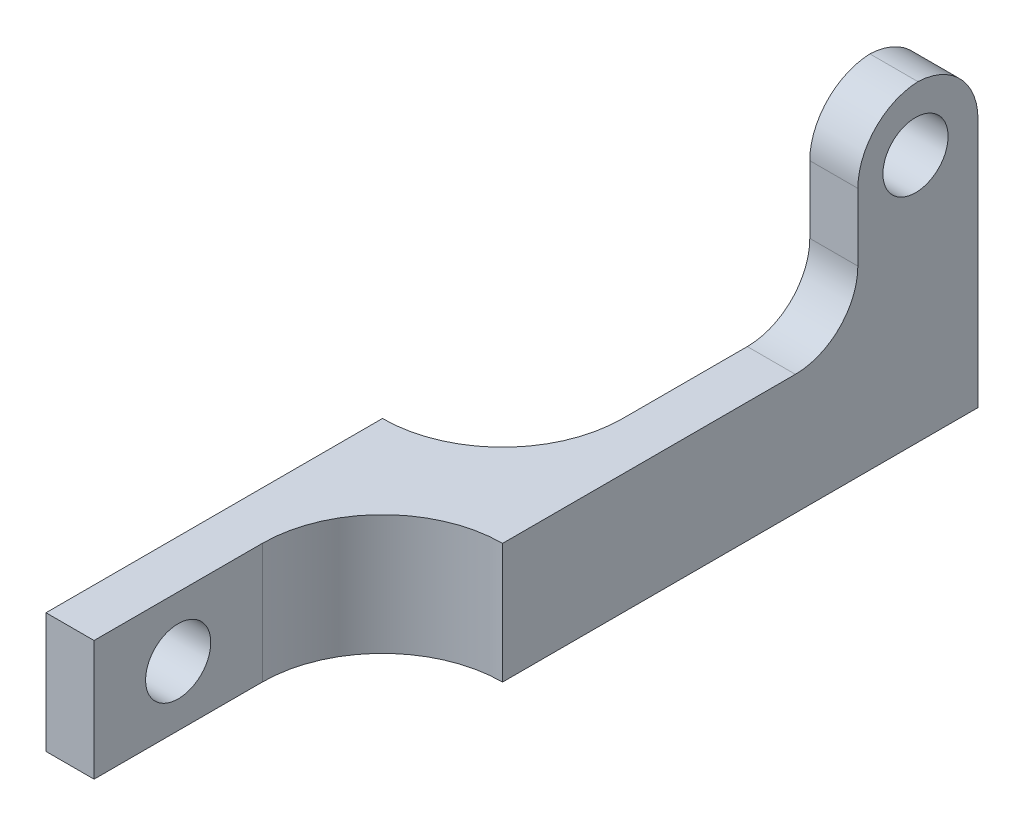
SolidWorks part; units mm, degrees
ref_plane "Front Plane" through (0, 0, 0) normal (0, 0, 1) x (1, 0, 0)
ref_plane "Top Plane" through (0, 0, 0) normal (0, 1, 0) x (1, 0, 0)
ref_plane "Right Plane" through (0, 0, 0) normal (1, 0, 0) x (0, 0, -1)
sketch "Sketch1" plane through (0, 0, 0) normal (0, 1, 0) x (1, 0, 0)
  line L0 (0, 0) -> (0, 22.225)
  line L1 (0, 22.225) -> (7.9375, 22.225)
  line L2 (7.9375, 22.225) -> (7.9375, 50.4584)
  line L3 (7.9375, 50.4584) -> (11.1125, 50.4584)
  line L4 (11.1125, 50.4584) -> (11.1125, 19.05)
  line L5 (11.1125, 19.05) -> (3.175, 19.05)
  line L6 (3.175, 19.05) -> (3.175, 0)
  line L7 (3.175, 0) -> (0, 0)
  dimension "D1" = 3.175
  dimension "D2" = 3.175
  dimension "D3" = 19.05
  dimension "D4" = 50.4584
  dimension "D5" = 7.9375
extrude "Boss-Extrude1" add sketch "Sketch1" along normal blind 7.9375
fillet "Fillet1" radius 7.9375 2 edges at (7.9375, 3.9688, -22.225) (3.175, 3.9688, -19.05)
sketch "Sketch6" plane through (0, 7.9375, 0) normal (0, 1, 0) x (1, 0, 0)
  line L0 (7.9375, 50.4584) -> (7.9375, 30.1625) construction
  line L1 (11.1125, 50.4584) -> (7.9375, 50.4584)
  line L2 (11.1125, 50.4584) -> (11.1125, 42.5209)
  line L3 (11.1125, 42.5209) -> (7.9375, 42.5209)
  line L4 (7.9375, 50.4584) -> (7.9375, 42.5209)
  dimension "D1" = 7.9375
extrude "Boss-Extrude2" add sketch "Sketch6" along normal blind 12.7
fillet "Fillet2" radius 4.1275 2 edges at (9.525, 20.6375, -50.4584) (9.525, 20.6375, -42.5209)
fillet "Fillet3" radius 4.1275 1 edges at (9.525, 7.9375, -42.5209)
hole_wizard "#6 Clearance Hole1" positions "Sketch2" profile "Sketch3" hole size "#6" standard "ANSI Inch" end condition through all
sketch "Sketch2" plane through (0, 0, 0) normal (1, 0, 0) x (0, 0, -1)
  line L0 (22.225, 0) -> (0, 0) construction
  line L1 (0, 7.9375) -> (0, 0) construction
  point P15 (5.5562, 3.9688)
  point P27 (46.3309, 16.51)
  dimension "D1" = 3.9688
  dimension "D2" = 5.5562
sketch "Sketch3" plane through (0, 3.9688, -5.5562) normal (0, 1, 0) x (0, 0, 1)
  line L0 (0, 0) -> (0, 11.1125)
  line L1 (0, 11.1125) -> (2.1526, 11.1125)
  line L2 (2.1526, 11.1125) -> (2.1526, 0)
  line L5 (2.1526, 0) -> (0, 0)
  line L11 (0, -6.35) -> (0, 107.95) construction
  dimension "Thru Hole Dia." = 4.3053
  dimension "Thru Hole Depth" = 11.1125
move or copy body "Body-Move/Copy1" [suppressed] bodies to move or copy 102
